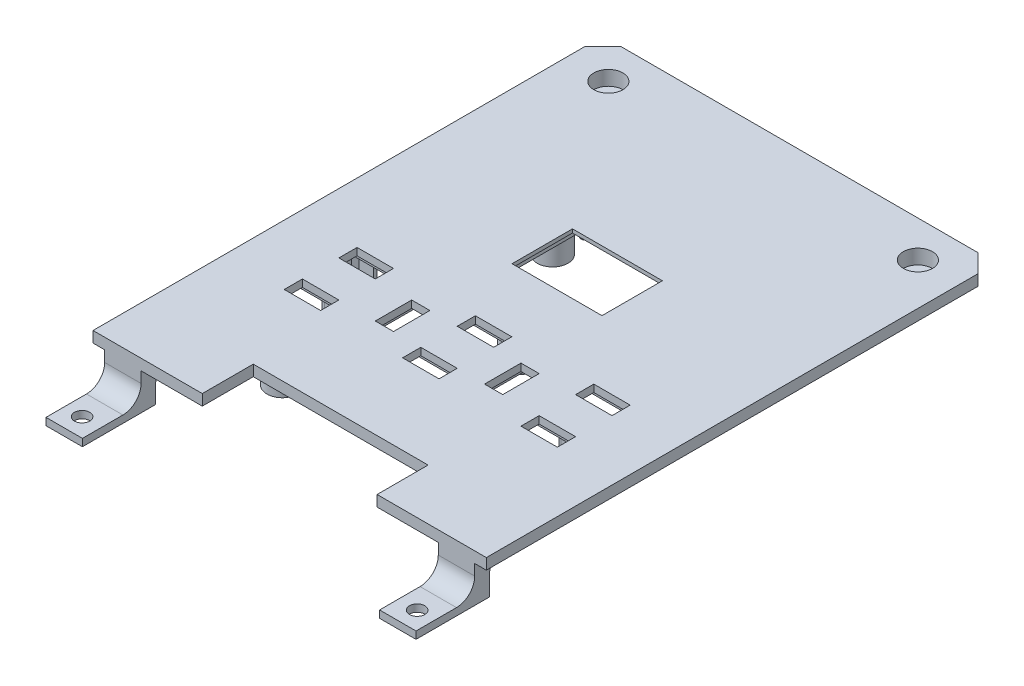
SolidWorks part; units mm, degrees
ref_plane "Alzado" through (0, 0, 0) normal (0, 0, 1) x (1, 0, 0)
ref_plane "Planta" through (0, 0, 0) normal (0, 1, 0) x (1, 0, 0)
ref_plane "Vista lateral" through (0, 0, 0) normal (1, 0, 0) x (0, 0, -1)
sketch "Croquis1" plane through (0, 0, 0) normal (0, 1, 0) x (1, 0, 0)
  line L0 (-54, 65) -> (-49, 70)
  line L1 (-24, -56) -> (24, -56)
  line L2 (-54, -65) -> (-54, 65)
  line L3 (-49, 70) -> (49, 70)
  line L4 (54, -65) -> (54, 65)
  line L5 (-54, -65) -> (54, 65) construction
  line L6 (-54, 65) -> (54, -65) construction
  line L7 (49, 70) -> (54, 65)
  line L10 (54, -65) -> (54, -70)
  line L11 (-12.35, 3.4) -> (12.35, 3.4)
  line L12 (-12.35, 3.4) -> (-12.35, 20)
  line L13 (-12.35, 20) -> (12.35, 20)
  line L14 (12.35, 3.4) -> (12.35, 20)
  line L15 (-12.35, 3.4) -> (12.35, 20) construction
  line L16 (-12.35, 20) -> (12.35, 3.4) construction
  line L17 (54, -70) -> (24, -70)
  line L18 (24, -70) -> (24, -56)
  line L19 (-54, -65) -> (-54, -70)
  line L20 (-54, -70) -> (-24, -70)
  line L21 (-24, -70) -> (-24, -56)
  line L22 (0, 70) -> (0, 29.5446) construction
  circle A0 centre (-42.5, 60) radius 2.1
  circle A1 centre (42.5, 60) radius 2.1
  circle A2 centre (-42.5, 60) radius 3.5 construction
  point P0 (0, 0)
  point P17 (0, 11.7)
  point P23 (0, 70)
  dimension "D3" = 4.2
  dimension "D13" = 7
  dimension "D14" = 85
  dimension "D15" = 10
  dimension "D1" = 45
  dimension "D2" = 14
  dimension "D4" = 45
  dimension "D5" = 108
  dimension "D6" = 98
  dimension "D7" = 140
  dimension "D8" = 50
  dimension "D9" = 16.6
  dimension "D10" = 24.7
  dimension "D11" = 70
  dimension "D12" = 48
extrude "Saliente-Extruir1" add sketch "Croquis1" along normal blind 3
sketch "Croquis2" plane through (0, 0, 0) normal (0, -1, 0) x (1, 0, 0)
  line L0 (12.35, -20) -> (-12.35, -3.4) construction
  line L1 (0, -11.7) -> (0, -54.3033) construction
  line L2 (13.5, 1.8) -> (-13.5, 1.8)
  line L3 (13.5, 1.8) -> (13.5, -25.2)
  line L4 (13.5, -25.2) -> (-13.5, -25.2)
  line L5 (-13.5, 1.8) -> (-13.5, -25.2)
  line L6 (13.5, 1.8) -> (-13.5, -25.2) construction
  line L7 (13.5, -25.2) -> (-13.5, 1.8) construction
  line L8 (0, -11.7) -> (-23.7061, -11.7) construction
  circle A0 centre (11.7, -23) radius 1.25
  circle A1 centre (-11.7, -23) radius 1.25
  circle A2 centre (-11.7, -0.4) radius 1.25
  circle A3 centre (11.7, -0.4) radius 1.25
  point P4 (0, -11.7)
  dimension "D3" = 2.5
  dimension "D4" = 2.2
  dimension "D5" = 1.8
  dimension "D1" = 27
  dimension "D2" = 27
extrude "Cortar-Extruir1" cut sketch "Croquis2" against normal blind 2
sketch "Croquis3" plane through (0, 0, 0) normal (0, -1, 0) x (1, 0, 0)
  line L0 (0, -25.2) -> (0, -33.1839) construction
  line L1 (-13.5, -25.2) -> (13.5, -25.2) construction
  line L2 (0, 0) -> (0, 45.7431) construction
  line L3 (49, -70) -> (-49, -70) construction
  line L4 (38.1521, 11.6119) -> (-42.6252, 11.6119) construction
  line L5 (-42.6252, 11.6119) -> (-42.6252, 35.6119) construction
  line L6 (-42.6252, 35.6119) -> (38.1521, 35.6119) construction
  line L7 (38.1521, 35.6119) -> (38.1521, 11.6119) construction
  circle A0 centre (-21, -23.2) radius 2
  circle A2 centre (21, -23.2) radius 4.25
  circle A3 centre (-21, -23.2) radius 4.25
  circle A4 centre (21, -23.2) radius 2
  circle A5 centre (-27, 45) radius 4.25
  circle A6 centre (27, 45) radius 4.25
  circle A7 centre (0, 7) radius 4.25
  circle A8 centre (0, 7) radius 2
  circle A9 centre (-27, 45) radius 2
  circle A10 centre (27, 45) radius 2
  dimension "D1" = 4
  dimension "D2" = 8.5
  dimension "D3" = 42
  dimension "D4" = 54
  dimension "D5" = 2
  dimension "D7" = 115
  dimension "D8" = 68.2
  dimension "D9" = 30.2
  dimension "D6" = 77
  dimension "D10" = 24
extrude "AlojamientoInsertos" add sketch "Croquis3" along normal blind 9
sketch "Croquis4" plane through (0, 3, 0) normal (0, 1, 0) x (1, 0, 0)
  line L0 (0, 0) -> (0, -7.2669) construction
  line L1 (-5, -34) -> (5, -34)
  line L2 (-5, -34) -> (-5, -29)
  line L3 (-5, -29) -> (5, -29)
  line L4 (5, -34) -> (5, -29)
  line L5 (-5, -34) -> (5, -29) construction
  line L6 (-5, -29) -> (5, -34) construction
  line L7 (27.5, -19) -> (37.5, -19)
  line L8 (27.5, -19) -> (27.5, -14)
  line L9 (27.5, -14) -> (37.5, -14)
  line L10 (37.5, -19) -> (37.5, -14)
  line L11 (27.5, -19) -> (37.5, -14) construction
  line L12 (27.5, -14) -> (37.5, -19) construction
  line L13 (27.5, -34) -> (37.5, -34)
  line L14 (27.5, -34) -> (27.5, -29)
  line L15 (27.5, -29) -> (37.5, -29)
  line L16 (37.5, -34) -> (37.5, -29)
  line L17 (27.5, -34) -> (37.5, -29) construction
  line L18 (27.5, -29) -> (37.5, -34) construction
  line L19 (-37.5, -34) -> (-27.5, -34)
  line L20 (-37.5, -34) -> (-37.5, -29)
  line L21 (-37.5, -29) -> (-27.5, -29)
  line L22 (-27.5, -34) -> (-27.5, -29)
  line L23 (-37.5, -34) -> (-27.5, -29) construction
  line L24 (-37.5, -29) -> (-27.5, -34) construction
  line L25 (-37.5, -19) -> (-27.5, -19)
  line L26 (-37.5, -19) -> (-37.5, -14)
  line L27 (-37.5, -14) -> (-27.5, -14)
  line L28 (-27.5, -19) -> (-27.5, -14)
  line L29 (-37.5, -19) -> (-27.5, -14) construction
  line L30 (-37.5, -14) -> (-27.5, -19) construction
  line L31 (0, -16.5) -> (0, -31.5) construction
  line L32 (49, 70) -> (-49, 70) construction
  line L35 (-5, -19) -> (5, -19)
  line L36 (-5, -19) -> (-5, -14)
  line L37 (-5, -14) -> (5, -14)
  line L38 (5, -19) -> (5, -14)
  line L39 (-5, -19) -> (5, -14) construction
  line L40 (-5, -14) -> (5, -19) construction
  line L41 (12.5, -29) -> (17.5, -29)
  line L42 (12.5, -29) -> (12.5, -19)
  line L43 (12.5, -19) -> (17.5, -19)
  line L44 (17.5, -29) -> (17.5, -19)
  line L45 (12.5, -29) -> (17.5, -19) construction
  line L46 (12.5, -19) -> (17.5, -29) construction
  line L47 (-17.5, -29) -> (-12.5, -29)
  line L48 (-17.5, -29) -> (-17.5, -19)
  line L49 (-17.5, -19) -> (-12.5, -19)
  line L50 (-12.5, -29) -> (-12.5, -19)
  line L51 (-17.5, -29) -> (-12.5, -19) construction
  line L52 (-17.5, -19) -> (-12.5, -29) construction
  circle A0 centre (0, -7) radius 4.25 construction
  point P0 (0, -31.5)
  point P5 (32.5, -16.5)
  point P10 (32.5, -31.5)
  point P15 (-32.5, -31.5)
  point P20 (-32.5, -16.5)
  point P26 (0, -24)
  point P27 (0, -16.5)
  point P33 (15, -24)
  point P41 (-15, -24)
  dimension "D1" = 10
  dimension "D2" = 5
  dimension "D3" = 94
  dimension "D4" = 32.5
  dimension "D5" = 15
  dimension "D6" = 30
  dimension "D7" = 7.5
  dimension "D8" = 10
  dimension "D9" = 5
  dimension "D10" = 17
extrude "Corte-Botones" cut sketch "Croquis4" against normal blind 10
sketch "Croquis5" plane through (0, 0, 0) normal (0, -1, 0) x (1, 0, 0)
  line L0 (12.5, 29) -> (12.5, 19) construction
  line L1 (12.5, 19) -> (17.5, 19) construction
  line L2 (-5, 14) -> (5, 14) construction
  line L3 (-17.5, 19) -> (-12.5, 19) construction
  line L4 (12.5, 29) -> (12.5, 19)
  line L5 (12.5, 19) -> (17.5, 19)
  line L6 (-5, 14) -> (5, 14)
  line L7 (-17.5, 19) -> (-12.5, 19)
  line L8 (-54, 70) -> (-54, -65)
  line L9 (-54, -65) -> (-49, -70)
  line L10 (-49, -70) -> (49, -70)
  line L11 (49, -70) -> (54, -65)
  line L12 (54, -65) -> (54, 70)
  line L13 (-27.5, 14) -> (-37.5, 14) construction
  line L14 (24, 56) -> (-24, 56)
  line L15 (-27.5, 14) -> (-37.5, 14)
  line L16 (-54, 70) -> (-54, -65)
  line L17 (-54, -65) -> (-49, -70)
  line L18 (-49, -70) -> (49, -70)
  line L19 (49, -70) -> (54, -65)
  line L20 (54, -65) -> (54, 70)
  line L24 (-27.5, 19) -> (-37.5, 19) construction
  line L25 (-37.5, 19) -> (-37.5, 14) construction
  line L27 (-27.5, 14) -> (-27.5, 19) construction
  line L28 (27.5, 29) -> (37.5, 29) construction
  line L29 (37.5, 29) -> (37.5, 34) construction
  line L30 (37.5, 34) -> (27.5, 34) construction
  line L31 (27.5, 34) -> (27.5, 29) construction
  line L32 (-5, 34) -> (-5, 29) construction
  line L33 (-5, 29) -> (5, 29) construction
  line L34 (5, 29) -> (5, 34) construction
  line L35 (5, 34) -> (-5, 34) construction
  line L36 (27.5, 14) -> (37.5, 14) construction
  line L37 (37.5, 14) -> (37.5, 19) construction
  line L38 (37.5, 19) -> (27.5, 19) construction
  line L39 (27.5, 19) -> (27.5, 14) construction
  line L40 (-27.5, 34) -> (-37.5, 34) construction
  line L41 (-27.5, 29) -> (-27.5, 34) construction
  line L42 (-37.5, 29) -> (-27.5, 29) construction
  line L43 (-37.5, 34) -> (-37.5, 29) construction
  line L44 (-27.5, 19) -> (-37.5, 19)
  line L45 (-37.5, 19) -> (-37.5, 14)
  line L47 (-27.5, 14) -> (-27.5, 19)
  line L48 (27.5, 29) -> (37.5, 29)
  line L49 (37.5, 29) -> (37.5, 34)
  line L50 (37.5, 34) -> (27.5, 34)
  line L51 (27.5, 34) -> (27.5, 29)
  line L52 (-5, 34) -> (-5, 29)
  line L53 (-5, 29) -> (5, 29)
  line L54 (5, 29) -> (5, 34)
  line L55 (5, 34) -> (-5, 34)
  line L56 (27.5, 14) -> (37.5, 14)
  line L57 (37.5, 14) -> (37.5, 19)
  line L58 (37.5, 19) -> (27.5, 19)
  line L59 (27.5, 19) -> (27.5, 14)
  line L60 (-27.5, 34) -> (-37.5, 34)
  line L61 (-27.5, 29) -> (-27.5, 34)
  line L62 (-37.5, 29) -> (-27.5, 29)
  line L63 (-37.5, 34) -> (-37.5, 29)
  line L64 (39.5, 20.5) -> (25.5, 20.5)
  line L65 (-39.5, 35.5) -> (-25.5, 35.5)
  line L66 (-39.5, 35.5) -> (-39.5, 27.5)
  line L67 (-39.5, 27.5) -> (-25.5, 27.5)
  line L68 (-25.5, 35.5) -> (-25.5, 27.5)
  line L69 (-39.5, 35.5) -> (-25.5, 27.5) construction
  line L70 (-39.5, 27.5) -> (-25.5, 35.5) construction
  line L71 (-7, 20.5) -> (7, 20.5)
  line L72 (-7, 20.5) -> (-7, 12.5)
  line L73 (-7, 12.5) -> (7, 12.5)
  line L74 (7, 20.5) -> (7, 12.5)
  line L75 (-7, 20.5) -> (7, 12.5) construction
  line L76 (-7, 12.5) -> (7, 20.5) construction
  line L77 (-7, 35.5) -> (7, 35.5)
  line L78 (-7, 35.5) -> (-7, 27.5)
  line L79 (-7, 27.5) -> (7, 27.5)
  line L80 (7, 35.5) -> (7, 27.5)
  line L81 (-7, 35.5) -> (7, 27.5) construction
  line L82 (-7, 27.5) -> (7, 35.5) construction
  line L83 (-39.5, 20.5) -> (-25.5, 20.5)
  line L84 (-39.5, 20.5) -> (-39.5, 12.5)
  line L85 (-39.5, 12.5) -> (-25.5, 12.5)
  line L86 (-25.5, 20.5) -> (-25.5, 12.5)
  line L87 (-39.5, 20.5) -> (-25.5, 12.5) construction
  line L88 (-39.5, 12.5) -> (-25.5, 20.5) construction
  line L89 (-7, 35.5) -> (7, 35.5)
  line L90 (-7, 35.5) -> (-7, 27.5)
  line L91 (-7, 27.5) -> (7, 27.5)
  line L92 (7, 35.5) -> (7, 27.5)
  line L93 (-7, 35.5) -> (7, 27.5) construction
  line L94 (-7, 27.5) -> (7, 35.5) construction
  line L95 (11, 17) -> (19, 17)
  line L96 (11, 17) -> (11, 31)
  line L97 (11, 31) -> (19, 31)
  line L98 (19, 17) -> (19, 31)
  line L99 (11, 17) -> (19, 31) construction
  line L100 (11, 31) -> (19, 17) construction
  line L105 (39.5, 20.5) -> (39.5, 12.5)
  line L106 (39.5, 12.5) -> (25.5, 12.5)
  line L107 (-19, 17) -> (-11, 17)
  line L108 (-19, 17) -> (-19, 31)
  line L109 (-19, 31) -> (-11, 31)
  line L110 (-11, 17) -> (-11, 31)
  line L111 (-19, 17) -> (-11, 31) construction
  line L112 (-19, 31) -> (-11, 17) construction
  line L113 (25.5, 20.5) -> (25.5, 12.5)
  line L114 (39.5, 20.5) -> (25.5, 12.5) construction
  line L115 (39.5, 12.5) -> (25.5, 20.5) construction
  line L116 (39.5, 35.5) -> (25.5, 35.5)
  line L117 (39.5, 35.5) -> (39.5, 27.5)
  line L118 (39.5, 27.5) -> (25.5, 27.5)
  line L119 (25.5, 35.5) -> (25.5, 27.5)
  line L120 (-24, 70) -> (-54, 70)
  line L121 (-24, 70) -> (-54, 70)
  line L122 (54, 70) -> (24, 70)
  line L123 (54, 70) -> (24, 70)
  line L124 (24, 70) -> (24, 56)
  line L125 (24, 70) -> (24, 56)
  line L126 (-24, 56) -> (-24, 70)
  line L127 (-24, 56) -> (-24, 70)
  line L128 (24, 56) -> (-24, 56)
  line L129 (39.5, 35.5) -> (25.5, 27.5) construction
  line L130 (39.5, 27.5) -> (25.5, 35.5) construction
  point P6 (-32.5, 31.5)
  point P9 (32.5, 16.5)
  point P12 (-32.5, 12.5)
  point P13 (-32.5, 14)
  point P20 (0, 16.5)
  point P30 (0, 31.5)
  point P39 (-32.5, 16.5)
  point P48 (0, 31.5)
  point P53 (0, 24)
  point P56 (-27.5, 16.5)
  point P57 (7, 16.5)
  point P60 (0, 34)
  point P61 (-15, 24)
  point P62 (37.5, 31.5)
  point P64 (5, 31.5)
  point P68 (-37.5, 31.5)
  point P69 (32.5, 31.5)
  point P70 (-32.5, 29)
  point P71 (-15, 19)
  point P73 (0, 14)
  point P78 (15, 24)
  point P88 (15, 19)
  point P90 (12.5, 24)
  point P92 (32.5, 29)
  point P93 (32.5, 20.5)
  point P94 (25.5, 16.5)
  point P95 (25.5, 31.5)
  point P101 (27.5, 16.5)
  point P102 (27.5, 31.5)
  dimension "D2" = 8
  dimension "D3" = 14
  dimension "D4" = 14
  dimension "D5" = 8
  dimension "D1" = 0
extrude "Cortar-Extruir3" cut sketch "Croquis5" against normal blind 1 contours L92 L89 L90 L91 | L74 L71 L72 L73 | L68 L65 L66 L67 | L86 L83 L84 L85 | L107 L110 L109 L108 | L64 L113 L106 L105 | L95 L98 L97 L96 | L116 L119 L118 L117 L51 L50 L49 L48 region at (39.3388, 0, 16.5) region at (-32.5, 0, 35.3388) region at (0, 0, 16.5) region at (0, 0, 35.3388) region at (-32.5, 0, 20.3388) region at (15, 0, 24) region at (-15, 0, 24) region at (39.3388, 0, 31.5)
sketch "Croquis11" plane through (0, 0, 0) normal (0, -1, 0) x (1, 0, 0)
  line L0 (-11, 17) -> (-11, 31) construction
  line L10 (-11, 17) -> (-11, 31)
  line L11 (-25.5, 27.5) -> (-25.5, 35.5) construction
  line L12 (-25.5, 35.5) -> (-39.5, 35.5) construction
  line L13 (-39.5, 35.5) -> (-39.5, 27.5) construction
  line L14 (-11, 17) -> (-11, 31)
  line L15 (-19, 17) -> (-11, 17)
  line L16 (-19, 31) -> (-19, 17)
  line L17 (-11, 31) -> (-19, 31)
  line L18 (-11, 17) -> (-11, 31)
  line L19 (-19, 17) -> (-11, 17)
  line L20 (-19, 31) -> (-19, 17)
  line L21 (-11, 31) -> (-19, 31)
  line L22 (-39.5, 27.5) -> (-25.5, 27.5) construction
  line L23 (-25.5, 12.5) -> (-25.5, 20.5) construction
  line L24 (-25.5, 20.5) -> (-39.5, 20.5) construction
  line L25 (-39.5, 20.5) -> (-39.5, 12.5) construction
  line L26 (-39.5, 12.5) -> (-25.5, 12.5) construction
  line L27 (-25.5, 27.5) -> (-25.5, 35.5)
  line L28 (-25.5, 35.5) -> (-39.5, 35.5)
  line L29 (-39.5, 35.5) -> (-39.5, 27.5)
  line L30 (-39.5, 27.5) -> (-25.5, 27.5)
  line L31 (-25.5, 12.5) -> (-25.5, 20.5)
  line L32 (-25.5, 20.5) -> (-39.5, 20.5)
  line L33 (-39.5, 20.5) -> (-39.5, 12.5)
  line L34 (-39.5, 12.5) -> (-25.5, 12.5)
  line L35 (39.5, 35.5) -> (25.5, 35.5) construction
  line L36 (25.5, 35.5) -> (25.5, 27.5) construction
  line L37 (25.5, 27.5) -> (39.5, 27.5) construction
  line L38 (39.5, 27.5) -> (39.5, 35.5) construction
  line L39 (39.5, 20.5) -> (25.5, 20.5) construction
  line L40 (25.5, 20.5) -> (25.5, 12.5) construction
  line L41 (25.5, 12.5) -> (39.5, 12.5) construction
  line L42 (39.5, 12.5) -> (39.5, 20.5) construction
  line L43 (11, 17) -> (19, 17) construction
  line L44 (19, 17) -> (19, 31) construction
  line L45 (19, 31) -> (11, 31) construction
  line L46 (11, 31) -> (11, 17) construction
  line L47 (7, 27.5) -> (7, 35.5) construction
  line L48 (7, 35.5) -> (-7, 35.5) construction
  line L49 (-7, 35.5) -> (-7, 27.5) construction
  line L50 (-7, 27.5) -> (7, 27.5) construction
  line L51 (7, 12.5) -> (7, 20.5) construction
  line L52 (7, 20.5) -> (-7, 20.5) construction
  line L53 (-7, 20.5) -> (-7, 12.5) construction
  line L54 (-7, 12.5) -> (7, 12.5) construction
  line L55 (39.5, 35.5) -> (25.5, 35.5)
  line L56 (25.5, 35.5) -> (25.5, 27.5)
  line L57 (25.5, 27.5) -> (39.5, 27.5)
  line L58 (39.5, 27.5) -> (39.5, 35.5)
  line L59 (39.5, 20.5) -> (25.5, 20.5)
  line L60 (25.5, 20.5) -> (25.5, 12.5)
  line L61 (25.5, 12.5) -> (39.5, 12.5)
  line L62 (39.5, 12.5) -> (39.5, 20.5)
  line L63 (11, 17) -> (19, 17)
  line L64 (19, 17) -> (19, 31)
  line L65 (19, 31) -> (11, 31)
  line L66 (11, 31) -> (11, 17)
  line L67 (7, 27.5) -> (7, 35.5)
  line L68 (7, 35.5) -> (-7, 35.5)
  line L69 (-7, 35.5) -> (-7, 27.5)
  line L70 (-7, 27.5) -> (7, 27.5)
  line L71 (7, 12.5) -> (7, 20.5)
  line L72 (7, 20.5) -> (-7, 20.5)
  line L73 (-7, 20.5) -> (-7, 12.5)
  line L74 (-7, 12.5) -> (7, 12.5)
  line L83 (41, 22) -> (24, 22)
  line L84 (24, 22) -> (24, 11)
  line L85 (24, 11) -> (41, 11)
  line L86 (41, 11) -> (41, 22)
  line L87 (41, 22) -> (24, 22)
  line L88 (24, 22) -> (24, 11)
  line L89 (24, 11) -> (41, 11)
  line L90 (41, 11) -> (41, 22)
  line L95 (41, 37) -> (24, 37)
  line L96 (24, 37) -> (24, 26)
  line L97 (24, 26) -> (41, 26)
  line L98 (41, 26) -> (41, 37)
  line L99 (41, 37) -> (24, 37)
  line L100 (24, 37) -> (24, 26)
  line L101 (24, 26) -> (41, 26)
  line L102 (41, 26) -> (41, 37)
  line L111 (9.5, 15.5) -> (20.5, 15.5)
  line L112 (20.5, 15.5) -> (20.5, 32.5)
  line L113 (20.5, 32.5) -> (9.5, 32.5)
  line L114 (9.5, 32.5) -> (9.5, 15.5)
  line L115 (9.5, 15.5) -> (20.5, 15.5)
  line L116 (20.5, 15.5) -> (20.5, 32.5)
  line L117 (20.5, 32.5) -> (9.5, 32.5)
  line L118 (9.5, 32.5) -> (9.5, 15.5)
  line L123 (8.5, 11) -> (8.5, 22)
  line L124 (8.5, 22) -> (-8.5, 22)
  line L125 (-8.5, 22) -> (-8.5, 11)
  line L126 (-8.5, 11) -> (8.5, 11)
  line L127 (8.5, 11) -> (8.5, 22)
  line L128 (8.5, 22) -> (-8.5, 22)
  line L129 (-8.5, 22) -> (-8.5, 11)
  line L130 (-8.5, 11) -> (8.5, 11)
  line L135 (-24, 11) -> (-24, 22)
  line L136 (-24, 22) -> (-41, 22)
  line L137 (-41, 22) -> (-41, 11)
  line L138 (-41, 11) -> (-24, 11)
  line L139 (-24, 11) -> (-24, 22)
  line L140 (-24, 22) -> (-41, 22)
  line L141 (-41, 22) -> (-41, 11)
  line L142 (-41, 11) -> (-24, 11)
  line L147 (-20.5, 15.5) -> (-9.5, 15.5)
  line L148 (-9.5, 15.5) -> (-9.5, 32.5)
  line L149 (-9.5, 32.5) -> (-20.5, 32.5)
  line L150 (-20.5, 32.5) -> (-20.5, 15.5)
  line L151 (-20.5, 15.5) -> (-9.5, 15.5)
  line L152 (-9.5, 15.5) -> (-9.5, 32.5)
  line L153 (-9.5, 32.5) -> (-20.5, 32.5)
  line L154 (-20.5, 32.5) -> (-20.5, 15.5)
  line L159 (-24, 26) -> (-24, 37)
  line L160 (-24, 37) -> (-41, 37)
  line L161 (-41, 37) -> (-41, 26)
  line L162 (-41, 26) -> (-24, 26)
  line L163 (-24, 26) -> (-24, 37)
  line L164 (-24, 37) -> (-41, 37)
  line L165 (-41, 37) -> (-41, 26)
  line L166 (-41, 26) -> (-24, 26)
  line L171 (8.5, 26) -> (8.5, 37)
  line L172 (8.5, 37) -> (-8.5, 37)
  line L173 (-8.5, 37) -> (-8.5, 26)
  line L174 (-8.5, 26) -> (8.5, 26)
  line L175 (8.5, 26) -> (8.5, 37)
  line L176 (8.5, 37) -> (-8.5, 37)
  line L177 (-8.5, 37) -> (-8.5, 26)
  line L178 (-8.5, 26) -> (8.5, 26)
  dimension "D1" = 0
  dimension "D2" = 1.5
  dimension "D3" = 1.5
  dimension "D4" = 1.5
  dimension "D5" = 1.5
  dimension "D6" = 1.5
  dimension "D7" = 1.5
  dimension "D8" = 1.5
  dimension "D9" = 1.5
extrude "Saliente-Extruir7" add sketch "Croquis11" along normal blind 1 contours L89 L90 L87 L88 L62 L61 L60 L59 | L117 L118 L115 L116 L66 L65 L64 L63 | L101 L102 L99 L100 L58 L57 L56 L55 | L129 L130 L127 L128 L74 L73 L72 L71 | L177 L178 L175 L176 L70 L69 L68 L67 | L153 L154 L151 L152 L21 L10 L19 L20 | L141 L142 L139 L140 L34 L33 L32 L31 | L165 L166 L163 L164 L30 L29 L28 L27 region at (40.7975, 0, 16.5) region at (40.7975, 0, 31.5) region at (9.7025, 0, 24) region at (0, 0, 11.2025) region at (-32.5, 0, 11.2025) region at (-20.2975, 0, 24) region at (-32.5, 0, 26.2025) region at (0, 0, 26.2025)
sketch "Croquis12" plane through (0, 0, 0) normal (0, -1, 0) x (1, 0, 0)
  line L3 (35, 24) -> (30, 24) construction
  line L4 (35, 22.5) -> (30, 22.5)
  line L5 (35, 25.5) -> (30, 25.5)
  line L9 (0, 14) -> (0, 34) construction
  line L13 (-35, 24) -> (-30, 24) construction
  line L14 (-35, 22.5) -> (-30, 22.5)
  line L15 (-35, 25.5) -> (-30, 25.5)
  line L19 (-5, 29) -> (5, 29) construction
  line L20 (5, 14) -> (-5, 14) construction
  line L21 (-5, 29) -> (5, 29)
  line L22 (5, 14) -> (-5, 14)
  line L23 (5, 34) -> (-5, 34) construction
  line L24 (5, 34) -> (-5, 34)
  line L28 (2.5, 36.75) -> (-2.5, 36.75) construction
  line L29 (2.5, 36) -> (-2.5, 36)
  line L30 (2.5, 37.5) -> (-2.5, 37.5)
  line L31 (-7, 27.5) -> (7, 27.5) construction
  line L32 (41, 11) -> (35, 11)
  line L33 (35, 11) -> (35, 12)
  line L34 (35, 12) -> (39, 12)
  line L35 (39, 12) -> (40, 13)
  line L36 (40, 13) -> (40, 17)
  line L37 (40, 17) -> (41, 17)
  line L38 (41, 17) -> (41, 11)
  line L39 (0, 24) -> (48.7463, 24) construction
  line L40 (-41, 17) -> (-41, 11)
  line L41 (-40, 17) -> (-41, 17)
  line L42 (-40, 13) -> (-40, 17)
  line L43 (-39, 12) -> (-40, 13)
  line L44 (-35, 12) -> (-39, 12)
  line L45 (-35, 11) -> (-35, 12)
  line L46 (-41, 11) -> (-35, 11)
  line L47 (41, 31) -> (41, 37)
  line L48 (40, 31) -> (41, 31)
  line L49 (40, 35) -> (40, 31)
  line L50 (39, 36) -> (40, 35)
  line L51 (35, 36) -> (39, 36)
  line L52 (35, 37) -> (35, 36)
  line L53 (41, 37) -> (35, 37)
  line L54 (-41, 37) -> (-35, 37)
  line L55 (-35, 37) -> (-35, 36)
  line L56 (-35, 36) -> (-39, 36)
  line L57 (-39, 36) -> (-40, 35)
  line L58 (-40, 35) -> (-40, 31)
  line L59 (-40, 31) -> (-41, 31)
  line L60 (-41, 31) -> (-41, 37)
  arc A2 (35, 22.5) -> (35, 25.5) centre (35, 24) ccw
  arc A3 (30, 25.5) -> (30, 22.5) centre (30, 24) ccw
  arc A8 (-35, 22.5) -> (-35, 25.5) centre (-35, 24) cw
  arc A9 (-30, 25.5) -> (-30, 22.5) centre (-30, 24) cw
  arc A12 (2.5, 36) -> (2.5, 37.5) centre (2.5, 36.75) ccw
  arc A13 (-2.5, 37.5) -> (-2.5, 36) centre (-2.5, 36.75) ccw
  point P2 (0, 36.75)
  point P7 (32.5, 24)
  point P34 (-32.5, 24)
  point P55 (0, 24)
  dimension "D4" = 9.25
  dimension "D5" = 1.5
  dimension "D6" = 6
  dimension "D9" = 41
  dimension "D11" = 30
  dimension "D8" = 1
  dimension "D12" = 0.75
  dimension "D2" = 5
  dimension "D3" = 5
  dimension "D7" = 4
  dimension "D10" = 13
extrude "Saliente-Extruir8" add sketch "Croquis12" along normal blind 5.5 contours L5 A3 L4 A2 | L30 A13 L29 A12 | L60 L59 L58 L57 L56 L55 L54 | L40 L46 L45 L44 L43 L42 L41 | L32 L33 L34 L35 L36 L37 L38 | L50 L49 L48 L47 L53 L52 L51 | A8 L15 A9 L14 region at (32.5, 0, 24) region at (0, 0, 36.75) region at (-40.5, 0, 16.9151) region at (-38, 0, 36.9151)
sketch "Croquis6" plane through (0, 0, 0) normal (0, -1, 0) x (1, 0, 0)
  line L0 (50.8, 70) -> (50.8, -63.6745)
  line L1 (24, 70) -> (54, 70) construction
  line L2 (50.8, -63.6745) -> (47.6745, -66.8)
  line L3 (47.6745, -66.8) -> (-47.6745, -66.8)
  line L4 (-47.6745, -66.8) -> (-50.8, -63.6745)
  line L5 (-50.8, -63.6745) -> (-50.8, 70)
  line L6 (-54, 70) -> (-24, 70) construction
  line L7 (54, -65) -> (49, -70) construction
  line L8 (-49, -70) -> (-54, -65) construction
  line L9 (54, 70) -> (54, -65) construction
  line L10 (49, -70) -> (-49, -70) construction
  line L11 (-54, -65) -> (-54, 70) construction
  line L12 (-50.8, 70) -> (-49.3, 70)
  line L13 (49.3, 70) -> (49.3, -63.0532)
  line L14 (49.3, -63.0532) -> (47.0532, -65.3)
  line L15 (47.0532, -65.3) -> (-47.0532, -65.3)
  line L16 (-47.0532, -65.3) -> (-49.3, -63.0532)
  line L17 (-49.3, -63.0532) -> (-49.3, 68.5)
  line L18 (-49.3, 70) -> (-49.3, 68.5)
  line L19 (-50.8, 70) -> (-48.2373, 70) construction
  line L20 (-49.3, 68.5) -> (-48.2373, 68.5) construction
  line L21 (50.8, 70) -> (49.3, 70)
  dimension "D1" = 3.2
  dimension "D2" = 3.2
  dimension "D3" = 3.2
  dimension "D4" = 3.2
  dimension "D5" = 3.2
  dimension "D6" = 1.5
extrude "Saliente-Extruir3" add sketch "Croquis6" along normal blind 1.5
sketch "Croquis7" plane through (0, 0, 0) normal (0, -1, 0) x (1, 0, 0)
  circle A0 centre (42.5, -60) radius 5
  circle A1 centre (-42.5, -60) radius 5
  dimension "D1" = 10
extrude "Saliente-Extruir4" add sketch "Croquis7" along normal blind 3 contours A0 | A1 region at (42.5, 0, -60) region at (-42.5, 0, -60)
sketch "Croquis8" plane through (0, 3, 0) normal (0, 1, 0) x (1, 0, 0)
  circle A0 centre (-42.5, 60) radius 4
  circle A1 centre (42.5, 60) radius 4
  dimension "D1" = 8
extrude "Cortar-Extruir4" cut sketch "Croquis8" against normal blind 4
sketch "Croquis9" plane through (0, 0, 70) normal (0, 0, 1) x (1, 0, 0)
  line L0 (50.8, -1.5) -> (50.8, -10)
  line L1 (50.8, -10) -> (40.8, -10)
  line L2 (40.8, -10) -> (40.8, 0)
  line L3 (24, 0) -> (49.3, 0) construction
  line L4 (40.8, 0) -> (49.3, 0)
  line L5 (49.3, 0) -> (49.3, -1.5)
  line L6 (49.3, -1.5) -> (50.8, -1.5)
  line L7 (0, 0) -> (0, -22.4343) construction
  line L8 (-49.3, -1.5) -> (-50.8, -1.5)
  line L9 (-49.3, 0) -> (-49.3, -1.5)
  line L10 (-40.8, 0) -> (-49.3, 0)
  line L11 (-40.8, -10) -> (-40.8, 0)
  line L12 (-50.8, -10) -> (-40.8, -10)
  line L13 (-50.8, -1.5) -> (-50.8, -10)
  dimension "D1" = 10
  dimension "D2" = 10
extrude "Saliente-Extruir5" add sketch "Croquis9" against normal blind 4
sketch "Croquis10" plane through (0, -10, 0) normal (0, -1, 0) x (1, 0, 0)
  line L0 (50.8, 70) -> (50.8, 86.1125)
  line L1 (50.8, 86.1125) -> (40.8, 86.1125)
  line L2 (40.8, 86.1125) -> (40.8, 70)
  line L3 (0, 0) -> (0, 133.4461) construction
  line L5 (40.8, 70) -> (50.8, 70)
  line L6 (-40.8, 70) -> (-50.8, 70)
  line L7 (-40.8, 86.1125) -> (-40.8, 70)
  line L8 (-50.8, 86.1125) -> (-40.8, 86.1125)
  line L9 (-50.8, 70) -> (-50.8, 86.1125)
  line L10 (49, -70) -> (-49, -70) construction
  circle A0 centre (46, 81) radius 2.1
  circle A1 centre (-46, 81) radius 2.1
  dimension "D1" = 151
  dimension "D2" = 92
  dimension "D3" = 4.2
extrude "Saliente-Extruir6" add sketch "Croquis10" against normal blind 2
fillet "Redondeo1" radius 5 4 edges at (45.05, 0, 66) (45.8, -8, 70) (-45.05, 0, 66) (-45.8, -8, 70)
